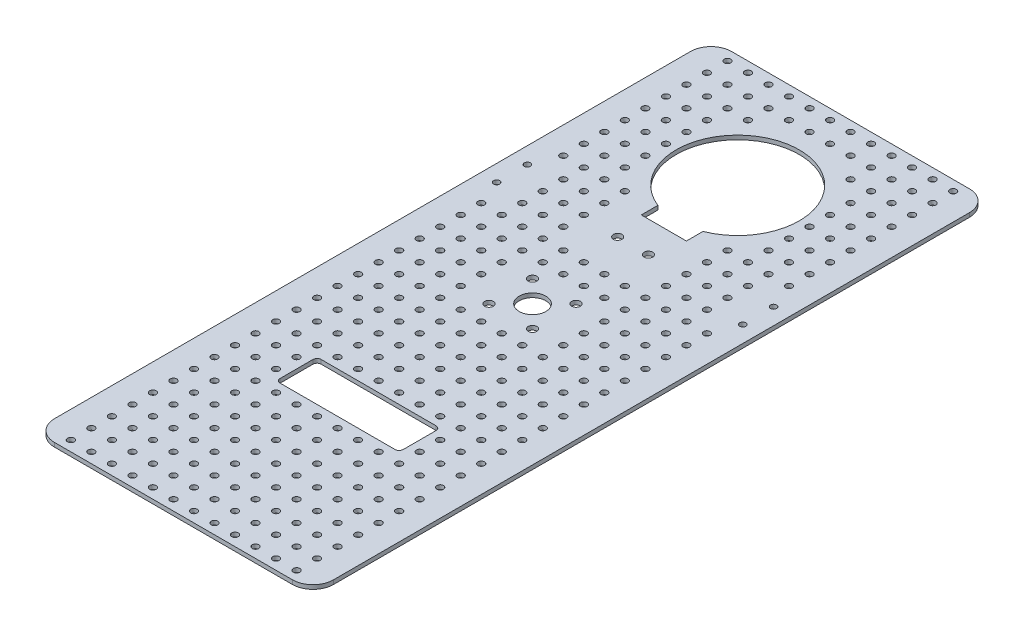
SolidWorks part; units mm, degrees
ref_plane "Спереди" through (0, 0, 0) normal (0, 0, 1) x (1, 0, 0)
ref_plane "Сверху" through (0, 0, 0) normal (0, 1, 0) x (1, 0, 0)
ref_plane "Справа" through (0, 0, 0) normal (1, 0, 0) x (0, 0, -1)
sketch "Эскиз1" plane through (0, 0, 0) normal (0, 1, 0) x (1, 0, 0)
  line L0 (0, 145) -> (0, -185) construction
  line L1 (-68, 145) -> (68, 145)
  line L2 (-68, 145) -> (-68, -185)
  line L3 (-68, -185) -> (68, -185)
  line L4 (68, 145) -> (68, -185)
  line L5 (-68, 0) -> (68, 0) construction
  dimension "D1" = 136
  dimension "D2" = 145
  dimension "D3" = 185
extrude "тело" add sketch "Эскиз1" along normal blind 2
sketch "Эскиз12" plane through (0, 2, 0) normal (0, 1, 0) x (1, 0, 0)
  line L0 (0, 145) -> (0, -185) construction
  line L1 (68, 145) -> (-68, 145) construction
  line L2 (-68, -185) -> (68, -185) construction
  line L3 (60, 47.5) -> (60, 32.5) construction
  line L4 (60, 40) -> (-60, 40) construction
  line L5 (-60, 47.5) -> (-60, 32.5) construction
  circle A0 centre (60, 47.5) radius 1.5
  circle A1 centre (-60, 47.5) radius 1.5
  circle A2 centre (-60, 32.5) radius 1.5
  circle A3 centre (60, 32.5) radius 1.5
  point P12 (-60, 40)
  point P17 (0, 40)
  dimension "D2" = 3
  dimension "D1" = 15
  dimension "D3" = 60
  dimension "D4" = 40
extrude "крепление подвески" cut sketch "Эскиз12" against normal through all
sketch "Эскиз9" plane through (0, 2, 0) normal (0, 1, 0) x (1, 0, 0)
  line L0 (0, -50) -> (0, 50) construction
  line L1 (68, 145) -> (-68, 145) construction
  line L3 (-10.6066, 0.6066) -> (0, -10) construction
  line L4 (0, -10) -> (0, 0) construction
  circle A0 centre (0, -10) radius 6.5
  circle A1 centre (0, -10) radius 15 construction
  circle A2 centre (-10.6066, 0.6066) radius 2.1
  circle A3 centre (10.6066, 0.6066) radius 2.1
  circle A4 centre (10.6066, -20.6066) radius 2.1
  circle A5 centre (-10.6066, -20.6066) radius 2.1
  point P21 (0, -10)
  dimension "D2" = 13
  dimension "D3" = 30
  dimension "D4" = 4.2
  dimension "D1" = 155
  dimension "D5" = 45
  dimension "D6" = 4
extrude "ось вращения качалки" cut sketch "Эскиз9" against normal through all
sketch "Эскиз5" plane through (0, 2, 0) normal (0, 1, 0) x (1, 0, 0)
  line L0 (-50, -171.5) -> (50, -121.5) construction
  line L1 (-50, -121.5) -> (50, -121.5) construction
  line L2 (-50, -121.5) -> (-50, -171.5) construction
  line L3 (-50, -171.5) -> (50, -171.5) construction
  line L4 (50, -121.5) -> (50, -171.5) construction
  line L5 (-50, -121.5) -> (50, -171.5) construction
  line L6 (-68, -185) -> (68, -185) construction
  circle A0 centre (-50, -121.5) radius 1.6
  circle A1 centre (50, -121.5) radius 1.6
  circle A2 centre (50, -171.5) radius 1.6
  circle A3 centre (-50, -171.5) radius 1.6
  point P12 (0, -146.5)
  dimension "D1" = 3.2
  dimension "D2" = 100
  dimension "D3" = 50
  dimension "D4" = 13.5
extrude "Крепление корпуса raspberry" [suppressed] cut sketch "Эскиз5" against normal through all
sketch "Эскиз15" [suppressed] plane through (0, 2, 0) normal (0, 1, 0) x (1, 0, 0)
  line L0 (-22.5, 138.75) -> (22.5, 138.75) construction
  line L1 (68, 145) -> (-68, 145) construction
  circle A0 centre (22.5, 138.75) radius 1.5
  circle A1 centre (-22.5, 138.75) radius 1.5
  point P6 (0, 138.75)
  dimension "D1" = 3
  dimension "D2" = 6.25
  dimension "D3" = 45
extrude "Крепление фронтальной камеры" [suppressed] cut sketch "Эскиз15" against normal up to next
sketch "Эскиз17" plane through (0, 2, 0) normal (0, 1, 0) x (1, 0, 0)
  line L1 (47.5, -137) -> (52.5, -137)
  line L2 (47.5, -137) -> (47.5, -147)
  line L3 (47.5, -147) -> (52.5, -147)
  line L4 (52.5, -137) -> (52.5, -147)
  line L5 (-68, -185) -> (68, -185) construction
  dimension "D1" = 38
  dimension "D2" = 10
  dimension "D3" = 5
extrude "Отверстие под провода питания raspberry" [suppressed] cut sketch "Эскиз17" against normal up to next
sketch "Эскиз18" plane through (0, 2, 0) normal (0, 1, 0) x (1, 0, 0)
  line L0 (0, 0) -> (0, 145) construction
  line L1 (68, 145) -> (-68, 145) construction
  line L2 (-11, 54) -> (11, 54)
  line L3 (11, 54) -> (11, 62.0894)
  line L5 (-11, 62.0894) -> (-11, 54)
  line L6 (68, 145) -> (-68, 145) construction
  line L12 (7.5, 39) -> (-7.5, 39) construction
  circle A1 centre (7.5, 39) radius 2.1
  circle A2 centre (-7.5, 39) radius 2.1
  arc A3 (11, 62.0894) -> (-11, 62.0894) centre (0, 90) ccw
  point P15 (0, 54)
  point P25 (0, 39)
  dimension "D8" = 4.2
  dimension "D3" = 60
  dimension "D1" = 22
  dimension "D2" = 36
  dimension "D4" = 55
  dimension "D9" = 15
  dimension "D10" = 15
fillet "Скругление4" radius 10 2 edges at (68, 1, -145) (-68, 1, -145)
fillet "Скругление6" [suppressed] radius 2
extrude "Вырез под манипулятор" cut sketch "Эскиз18" against normal up to next
fillet "Скругление9" radius 10 2 edges at (68, 1, 185) (-68, 1, 185)
sketch "Эскиз20" plane through (0, 2, 0) normal (0, 1, 0) x (1, 0, 0)
  line L0 (-17.5, -181) -> (17.5, -181) construction
  line L1 (-58, -185) -> (58, -185) construction
  circle A0 centre (-17.5, -181) radius 1.5
  circle A1 centre (17.5, -181) radius 1.5
  point P4 (0, -181)
  point P7 (0, -185)
  dimension "D1" = 3
  dimension "D2" = 4
  dimension "D3" = 35
extrude "Крепление платы раздачи питания с креплением ХТ60" [suppressed] cut sketch "Эскиз20" against normal up to next
sketch "Эскиз21" [suppressed] plane through (0, 2, 0) normal (0, 1, 0) x (1, 0, 0)
  line L0 (-58, -185) -> (58, -185) construction
  line L1 (-35, -43.5) -> (35, -43.5) construction
  line L2 (-35, -43.5) -> (-35, -73.5) construction
  line L3 (-35, -73.5) -> (35, -73.5) construction
  line L4 (35, -43.5) -> (35, -73.5) construction
  circle A0 centre (-35, -43.5) radius 1.6
  circle A1 centre (-35, -73.5) radius 1.6
  circle A2 centre (35, -73.5) radius 1.6
  circle A3 centre (35, -43.5) radius 1.6
  circle A4 centre (50, -121.5) radius 1.6 construction
  point P4 (0, -73.5)
  point P7 (0, -185)
  dimension "D3" = 3.2
  dimension "D1" = 30
  dimension "D2" = 70
  dimension "D4" = 48
extrude "Крепление подставки ServoBoard" [suppressed] cut sketch "Эскиз21" against normal up to next
sketch "Эскиз22" plane through (0, 2, 0) normal (0, 1, 0) x (1, 0, 0)
  line L0 (0, -185) -> (0, 145) construction
  line L1 (-58, -185) -> (58, -185) construction
  line L2 (58, 145) -> (-58, 145) construction
  circle A0 centre (-5, -180) radius 1.6
  circle A1 centre (-15, -180) radius 1.6
  circle A2 centre (-25, -180) radius 1.6
  circle A3 centre (-35, -180) radius 1.6
  circle A4 centre (-45, -180) radius 1.6
  circle A5 centre (-55, -180) radius 1.6
  circle A6 centre (-65, -180) radius 1.6 construction
  circle A7 centre (5, -180) radius 1.6
  circle A8 centre (15, -180) radius 1.6
  circle A9 centre (25, -180) radius 1.6
  circle A10 centre (35, -180) radius 1.6
  circle A11 centre (45, -180) radius 1.6
  circle A12 centre (55, -180) radius 1.6
  circle A13 centre (65, -180) radius 1.6 construction
  circle A14 centre (-5, -170) radius 1.6
  circle A15 centre (-15, -170) radius 1.6
  circle A16 centre (-25, -170) radius 1.6
  circle A17 centre (-35, -170) radius 1.6
  circle A18 centre (-45, -170) radius 1.6
  circle A19 centre (-55, -170) radius 1.6
  circle A20 centre (-65, -170) radius 1.6 construction
  circle A21 centre (5, -170) radius 1.6
  circle A22 centre (15, -170) radius 1.6
  circle A23 centre (25, -170) radius 1.6
  circle A24 centre (35, -170) radius 1.6
  circle A25 centre (45, -170) radius 1.6
  circle A26 centre (55, -170) radius 1.6
  circle A27 centre (65, -170) radius 1.6 construction
  circle A28 centre (-5, -160) radius 1.6
  circle A29 centre (-15, -160) radius 1.6
  circle A30 centre (-25, -160) radius 1.6
  circle A31 centre (-35, -160) radius 1.6
  circle A32 centre (-45, -160) radius 1.6
  circle A33 centre (-55, -160) radius 1.6
  circle A34 centre (-65, -160) radius 1.6 construction
  circle A35 centre (5, -160) radius 1.6
  circle A36 centre (15, -160) radius 1.6
  circle A37 centre (25, -160) radius 1.6
  circle A38 centre (35, -160) radius 1.6
  circle A39 centre (45, -160) radius 1.6
  circle A40 centre (55, -160) radius 1.6
  circle A41 centre (65, -160) radius 1.6 construction
  circle A42 centre (-5, -150) radius 1.6
  circle A43 centre (-15, -150) radius 1.6
  circle A44 centre (-25, -150) radius 1.6
  circle A45 centre (-35, -150) radius 1.6
  circle A46 centre (-45, -150) radius 1.6
  circle A47 centre (-55, -150) radius 1.6
  circle A48 centre (-65, -150) radius 1.6 construction
  circle A49 centre (5, -150) radius 1.6
  circle A50 centre (15, -150) radius 1.6
  circle A51 centre (25, -150) radius 1.6
  circle A52 centre (35, -150) radius 1.6
  circle A53 centre (45, -150) radius 1.6
  circle A54 centre (55, -150) radius 1.6
  circle A55 centre (65, -150) radius 1.6 construction
  circle A56 centre (-5, -140) radius 1.6
  circle A57 centre (-15, -140) radius 1.6
  circle A58 centre (-25, -140) radius 1.6
  circle A59 centre (-35, -140) radius 1.6
  circle A60 centre (-45, -140) radius 1.6
  circle A61 centre (-55, -140) radius 1.6
  circle A62 centre (-65, -140) radius 1.6 construction
  circle A63 centre (5, -140) radius 1.6
  circle A64 centre (15, -140) radius 1.6
  circle A65 centre (25, -140) radius 1.6
  circle A66 centre (35, -140) radius 1.6
  circle A67 centre (45, -140) radius 1.6
  circle A68 centre (55, -140) radius 1.6
  circle A69 centre (65, -140) radius 1.6 construction
  circle A70 centre (-5, -130) radius 1.6
  circle A71 centre (-15, -130) radius 1.6
  circle A72 centre (-25, -130) radius 1.6
  circle A73 centre (-35, -130) radius 1.6
  circle A74 centre (-45, -130) radius 1.6
  circle A75 centre (-55, -130) radius 1.6
  circle A76 centre (-65, -130) radius 1.6 construction
  circle A77 centre (5, -130) radius 1.6
  circle A78 centre (15, -130) radius 1.6
  circle A79 centre (25, -130) radius 1.6
  circle A80 centre (35, -130) radius 1.6
  circle A81 centre (45, -130) radius 1.6
  circle A82 centre (55, -130) radius 1.6
  circle A83 centre (65, -130) radius 1.6 construction
  circle A84 centre (-5, -120) radius 1.6
  circle A85 centre (-15, -120) radius 1.6
  circle A86 centre (-25, -120) radius 1.6
  circle A87 centre (-35, -120) radius 1.6
  circle A88 centre (-45, -120) radius 1.6
  circle A89 centre (-55, -120) radius 1.6
  circle A90 centre (-65, -120) radius 1.6 construction
  circle A91 centre (5, -120) radius 1.6
  circle A92 centre (15, -120) radius 1.6
  circle A93 centre (25, -120) radius 1.6
  circle A94 centre (35, -120) radius 1.6
  circle A95 centre (45, -120) radius 1.6
  circle A96 centre (55, -120) radius 1.6
  circle A97 centre (65, -120) radius 1.6 construction
  circle A98 centre (-5, -110) radius 1.6
  circle A99 centre (-15, -110) radius 1.6
  circle A100 centre (-25, -110) radius 1.6
  circle A101 centre (-35, -110) radius 1.6
  circle A102 centre (-45, -110) radius 1.6
  circle A103 centre (-55, -110) radius 1.6
  circle A104 centre (-65, -110) radius 1.6 construction
  circle A105 centre (5, -110) radius 1.6
  circle A106 centre (15, -110) radius 1.6
  circle A107 centre (25, -110) radius 1.6
  circle A108 centre (35, -110) radius 1.6
  circle A109 centre (45, -110) radius 1.6
  circle A110 centre (55, -110) radius 1.6
  circle A111 centre (65, -110) radius 1.6 construction
  circle A112 centre (-5, -100) radius 1.6 construction
  circle A113 centre (-15, -100) radius 1.6 construction
  circle A114 centre (-25, -100) radius 1.6 construction
  circle A115 centre (-35, -100) radius 1.6
  circle A116 centre (-45, -100) radius 1.6
  circle A117 centre (-55, -100) radius 1.6
  circle A118 centre (-65, -100) radius 1.6 construction
  circle A119 centre (5, -100) radius 1.6 construction
  circle A120 centre (15, -100) radius 1.6 construction
  circle A121 centre (25, -100) radius 1.6 construction
  circle A122 centre (35, -100) radius 1.6
  circle A123 centre (45, -100) radius 1.6
  circle A124 centre (55, -100) radius 1.6
  circle A125 centre (65, -100) radius 1.6 construction
  circle A126 centre (-5, -90) radius 1.6 construction
  circle A127 centre (-15, -90) radius 1.6 construction
  circle A128 centre (-25, -90) radius 1.6 construction
  circle A129 centre (-35, -90) radius 1.6
  circle A130 centre (-45, -90) radius 1.6
  circle A131 centre (-55, -90) radius 1.6
  circle A132 centre (-65, -90) radius 1.6 construction
  circle A133 centre (5, -90) radius 1.6 construction
  circle A134 centre (15, -90) radius 1.6 construction
  circle A135 centre (25, -90) radius 1.6 construction
  circle A136 centre (35, -90) radius 1.6
  circle A137 centre (45, -90) radius 1.6
  circle A138 centre (55, -90) radius 1.6
  circle A139 centre (65, -90) radius 1.6 construction
  circle A140 centre (-5, -80) radius 1.6
  circle A141 centre (-15, -80) radius 1.6
  circle A142 centre (-25, -80) radius 1.6
  circle A143 centre (-35, -80) radius 1.6
  circle A144 centre (-45, -80) radius 1.6
  circle A145 centre (-55, -80) radius 1.6
  circle A146 centre (-65, -80) radius 1.6 construction
  circle A147 centre (5, -80) radius 1.6
  circle A148 centre (15, -80) radius 1.6
  circle A149 centre (25, -80) radius 1.6
  circle A150 centre (35, -80) radius 1.6
  circle A151 centre (45, -80) radius 1.6
  circle A152 centre (55, -80) radius 1.6
  circle A153 centre (65, -80) radius 1.6 construction
  circle A154 centre (-5, -70) radius 1.6
  circle A155 centre (-15, -70) radius 1.6
  circle A156 centre (-25, -70) radius 1.6
  circle A157 centre (-35, -70) radius 1.6
  circle A158 centre (-45, -70) radius 1.6
  circle A159 centre (-55, -70) radius 1.6
  circle A160 centre (-65, -70) radius 1.6 construction
  circle A161 centre (5, -70) radius 1.6
  circle A162 centre (15, -70) radius 1.6
  circle A163 centre (25, -70) radius 1.6
  circle A164 centre (35, -70) radius 1.6
  circle A165 centre (45, -70) radius 1.6
  circle A166 centre (55, -70) radius 1.6
  circle A167 centre (65, -70) radius 1.6 construction
  circle A168 centre (-5, -60) radius 1.6
  circle A169 centre (-15, -60) radius 1.6
  circle A170 centre (-25, -60) radius 1.6
  circle A171 centre (-35, -60) radius 1.6
  circle A172 centre (-45, -60) radius 1.6
  circle A173 centre (-55, -60) radius 1.6
  circle A174 centre (-65, -60) radius 1.6 construction
  circle A175 centre (5, -60) radius 1.6
  circle A176 centre (15, -60) radius 1.6
  circle A177 centre (25, -60) radius 1.6
  circle A178 centre (35, -60) radius 1.6
  circle A179 centre (45, -60) radius 1.6
  circle A180 centre (55, -60) radius 1.6
  circle A181 centre (65, -60) radius 1.6 construction
  circle A182 centre (-5, -50) radius 1.6
  circle A183 centre (-15, -50) radius 1.6
  circle A184 centre (-25, -50) radius 1.6
  circle A185 centre (-35, -50) radius 1.6
  circle A186 centre (-45, -50) radius 1.6
  circle A187 centre (-55, -50) radius 1.6
  circle A188 centre (-65, -50) radius 1.6 construction
  circle A189 centre (5, -50) radius 1.6
  circle A190 centre (15, -50) radius 1.6
  circle A191 centre (25, -50) radius 1.6
  circle A192 centre (35, -50) radius 1.6
  circle A193 centre (45, -50) radius 1.6
  circle A194 centre (55, -50) radius 1.6
  circle A195 centre (65, -50) radius 1.6 construction
  circle A196 centre (-5, -40) radius 1.6
  circle A197 centre (-15, -40) radius 1.6
  circle A198 centre (-25, -40) radius 1.6
  circle A199 centre (-35, -40) radius 1.6
  circle A200 centre (-45, -40) radius 1.6
  circle A201 centre (-55, -40) radius 1.6
  circle A202 centre (-65, -40) radius 1.6 construction
  circle A203 centre (5, -40) radius 1.6
  circle A204 centre (15, -40) radius 1.6
  circle A205 centre (25, -40) radius 1.6
  circle A206 centre (35, -40) radius 1.6
  circle A207 centre (45, -40) radius 1.6
  circle A208 centre (55, -40) radius 1.6
  circle A209 centre (65, -40) radius 1.6 construction
  circle A210 centre (-5, -30) radius 1.6
  circle A211 centre (-15, -30) radius 1.6
  circle A212 centre (-25, -30) radius 1.6
  circle A213 centre (-35, -30) radius 1.6
  circle A214 centre (-45, -30) radius 1.6
  circle A215 centre (-55, -30) radius 1.6
  circle A216 centre (-65, -30) radius 1.6 construction
  circle A217 centre (5, -30) radius 1.6
  circle A218 centre (15, -30) radius 1.6
  circle A219 centre (25, -30) radius 1.6
  circle A220 centre (35, -30) radius 1.6
  circle A221 centre (45, -30) radius 1.6
  circle A222 centre (55, -30) radius 1.6
  circle A223 centre (65, -30) radius 1.6 construction
  circle A226 centre (-25, -20) radius 1.6
  circle A227 centre (-35, -20) radius 1.6
  circle A228 centre (-45, -20) radius 1.6
  circle A229 centre (-55, -20) radius 1.6
  circle A230 centre (-65, -20) radius 1.6 construction
  circle A233 centre (25, -20) radius 1.6
  circle A234 centre (35, -20) radius 1.6
  circle A235 centre (45, -20) radius 1.6
  circle A236 centre (55, -20) radius 1.6
  circle A237 centre (65, -20) radius 1.6 construction
  circle A240 centre (-25, -10) radius 1.6
  circle A241 centre (-35, -10) radius 1.6
  circle A242 centre (-45, -10) radius 1.6
  circle A243 centre (-55, -10) radius 1.6
  circle A244 centre (-65, -10) radius 1.6 construction
  circle A247 centre (25, -10) radius 1.6
  circle A248 centre (35, -10) radius 1.6
  circle A249 centre (45, -10) radius 1.6
  circle A250 centre (55, -10) radius 1.6
  circle A251 centre (65, -10) radius 1.6 construction
  circle A254 centre (-25, 0) radius 1.6
  circle A255 centre (-35, 0) radius 1.6
  circle A256 centre (-45, 0) radius 1.6
  circle A257 centre (-55, 0) radius 1.6
  circle A258 centre (-65, 0) radius 1.6 construction
  circle A261 centre (25, 0) radius 1.6
  circle A262 centre (35, 0) radius 1.6
  circle A263 centre (45, 0) radius 1.6
  circle A264 centre (55, 0) radius 1.6
  circle A265 centre (65, 0) radius 1.6 construction
  circle A266 centre (-5, 10) radius 1.6
  circle A267 centre (-15, 10) radius 1.6
  circle A268 centre (-25, 10) radius 1.6
  circle A269 centre (-35, 10) radius 1.6
  circle A270 centre (-45, 10) radius 1.6
  circle A271 centre (-55, 10) radius 1.6
  circle A272 centre (-65, 10) radius 1.6 construction
  circle A273 centre (5, 10) radius 1.6
  circle A274 centre (15, 10) radius 1.6
  circle A275 centre (25, 10) radius 1.6
  circle A276 centre (35, 10) radius 1.6
  circle A277 centre (45, 10) radius 1.6
  circle A278 centre (55, 10) radius 1.6
  circle A279 centre (65, 10) radius 1.6 construction
  circle A280 centre (-5, 20) radius 1.6
  circle A281 centre (-15, 20) radius 1.6
  circle A282 centre (-25, 20) radius 1.6
  circle A283 centre (-35, 20) radius 1.6
  circle A284 centre (-45, 20) radius 1.6
  circle A285 centre (-55, 20) radius 1.6
  circle A286 centre (-65, 20) radius 1.6 construction
  circle A287 centre (5, 20) radius 1.6
  circle A288 centre (15, 20) radius 1.6
  circle A289 centre (25, 20) radius 1.6
  circle A290 centre (35, 20) radius 1.6
  circle A291 centre (45, 20) radius 1.6
  circle A292 centre (55, 20) radius 1.6
  circle A293 centre (65, 20) radius 1.6 construction
  circle A294 centre (-5, 30) radius 1.6 construction
  circle A295 centre (-15, 30) radius 1.6 construction
  circle A296 centre (-25, 30) radius 1.6
  circle A297 centre (-35, 30) radius 1.6
  circle A298 centre (-45, 30) radius 1.6
  circle A299 centre (-55, 30) radius 1.6 construction
  circle A300 centre (-65, 30) radius 1.6 construction
  circle A301 centre (5, 30) radius 1.6 construction
  circle A302 centre (15, 30) radius 1.6 construction
  circle A303 centre (25, 30) radius 1.6
  circle A304 centre (35, 30) radius 1.6
  circle A305 centre (45, 30) radius 1.6
  circle A306 centre (55, 30) radius 1.6 construction
  circle A307 centre (65, 30) radius 1.6 construction
  circle A309 centre (-15, 40) radius 1.6 construction
  circle A310 centre (-25, 40) radius 1.6
  circle A311 centre (-35, 40) radius 1.6
  circle A312 centre (-45, 40) radius 1.6
  circle A313 centre (-55, 40) radius 1.6 construction
  circle A314 centre (-65, 40) radius 1.6 construction
  circle A316 centre (15, 40) radius 1.6 construction
  circle A317 centre (25, 40) radius 1.6
  circle A318 centre (35, 40) radius 1.6
  circle A319 centre (45, 40) radius 1.6
  circle A320 centre (55, 40) radius 1.6 construction
  circle A321 centre (65, 40) radius 1.6 construction
  circle A323 centre (-15, 50) radius 1.6 construction
  circle A324 centre (-25, 50) radius 1.6
  circle A325 centre (-35, 50) radius 1.6
  circle A326 centre (-45, 50) radius 1.6
  circle A327 centre (-55, 50) radius 1.6 construction
  circle A328 centre (-65, 50) radius 1.6 construction
  circle A330 centre (15, 50) radius 1.6 construction
  circle A331 centre (25, 50) radius 1.6
  circle A332 centre (35, 50) radius 1.6
  circle A333 centre (45, 50) radius 1.6
  circle A334 centre (55, 50) radius 1.6 construction
  circle A335 centre (65, 50) radius 1.6 construction
  circle A337 centre (-15, 60) radius 1.6 construction
  circle A338 centre (-25, 60) radius 1.6
  circle A339 centre (-35, 60) radius 1.6
  circle A340 centre (-45, 60) radius 1.6
  circle A341 centre (-55, 60) radius 1.6
  circle A342 centre (-65, 60) radius 1.6 construction
  circle A344 centre (15, 60) radius 1.6 construction
  circle A345 centre (25, 60) radius 1.6
  circle A346 centre (35, 60) radius 1.6
  circle A347 centre (45, 60) radius 1.6
  circle A348 centre (55, 60) radius 1.6
  circle A349 centre (65, 60) radius 1.6 construction
  circle A352 centre (-25, 70) radius 1.6 construction
  circle A353 centre (-35, 70) radius 1.6
  circle A354 centre (-45, 70) radius 1.6
  circle A355 centre (-55, 70) radius 1.6
  circle A356 centre (-65, 70) radius 1.6 construction
  circle A359 centre (25, 70) radius 1.6 construction
  circle A360 centre (35, 70) radius 1.6
  circle A361 centre (45, 70) radius 1.6
  circle A362 centre (55, 70) radius 1.6
  circle A363 centre (65, 70) radius 1.6 construction
  circle A367 centre (-35, 80) radius 1.6
  circle A368 centre (-45, 80) radius 1.6
  circle A369 centre (-55, 80) radius 1.6
  circle A370 centre (-65, 80) radius 1.6 construction
  circle A374 centre (35, 80) radius 1.6
  circle A375 centre (45, 80) radius 1.6
  circle A376 centre (55, 80) radius 1.6
  circle A377 centre (65, 80) radius 1.6 construction
  circle A381 centre (-35, 90) radius 1.6
  circle A382 centre (-45, 90) radius 1.6
  circle A383 centre (-55, 90) radius 1.6
  circle A384 centre (-65, 90) radius 1.6 construction
  circle A388 centre (35, 90) radius 1.6
  circle A389 centre (45, 90) radius 1.6
  circle A390 centre (55, 90) radius 1.6
  circle A391 centre (65, 90) radius 1.6 construction
  circle A395 centre (-35, 100) radius 1.6
  circle A396 centre (-45, 100) radius 1.6
  circle A397 centre (-55, 100) radius 1.6
  circle A398 centre (-65, 100) radius 1.6 construction
  circle A402 centre (35, 100) radius 1.6
  circle A403 centre (45, 100) radius 1.6
  circle A404 centre (55, 100) radius 1.6
  circle A405 centre (65, 100) radius 1.6 construction
  circle A408 centre (-25, 110) radius 1.6 construction
  circle A409 centre (-35, 110) radius 1.6
  circle A410 centre (-45, 110) radius 1.6
  circle A411 centre (-55, 110) radius 1.6
  circle A412 centre (-65, 110) radius 1.6 construction
  circle A415 centre (25, 110) radius 1.6 construction
  circle A416 centre (35, 110) radius 1.6
  circle A417 centre (45, 110) radius 1.6
  circle A418 centre (55, 110) radius 1.6
  circle A419 centre (65, 110) radius 1.6 construction
  circle A421 centre (-15, 120) radius 1.6 construction
  circle A422 centre (-25, 120) radius 1.6
  circle A423 centre (-35, 120) radius 1.6
  circle A424 centre (-45, 120) radius 1.6
  circle A425 centre (-55, 120) radius 1.6
  circle A426 centre (-65, 120) radius 1.6 construction
  circle A428 centre (15, 120) radius 1.6 construction
  circle A429 centre (25, 120) radius 1.6
  circle A430 centre (35, 120) radius 1.6
  circle A431 centre (45, 120) radius 1.6
  circle A432 centre (55, 120) radius 1.6
  circle A433 centre (65, 120) radius 1.6 construction
  circle A434 centre (-5, 130) radius 1.6
  circle A435 centre (-15, 130) radius 1.6
  circle A436 centre (-25, 130) radius 1.6
  circle A437 centre (-35, 130) radius 1.6
  circle A438 centre (-45, 130) radius 1.6
  circle A439 centre (-55, 130) radius 1.6
  circle A440 centre (-65, 130) radius 1.6 construction
  circle A441 centre (5, 130) radius 1.6
  circle A442 centre (15, 130) radius 1.6
  circle A443 centre (25, 130) radius 1.6
  circle A444 centre (35, 130) radius 1.6
  circle A445 centre (45, 130) radius 1.6
  circle A446 centre (55, 130) radius 1.6
  circle A447 centre (65, 130) radius 1.6 construction
  circle A448 centre (-5, 140) radius 1.6
  circle A449 centre (-15, 140) radius 1.6
  circle A450 centre (-25, 140) radius 1.6
  circle A451 centre (-35, 140) radius 1.6
  circle A452 centre (-45, 140) radius 1.6
  circle A453 centre (-55, 140) radius 1.6
  circle A454 centre (-65, 140) radius 1.6 construction
  circle A455 centre (5, 140) radius 1.6
  circle A456 centre (15, 140) radius 1.6
  circle A457 centre (25, 140) radius 1.6
  circle A458 centre (35, 140) radius 1.6
  circle A459 centre (45, 140) radius 1.6
  circle A460 centre (55, 140) radius 1.6
  circle A461 centre (65, 140) radius 1.6 construction
  circle A462 centre (-5, -20) radius 1.6 construction
  circle A463 centre (-15, -20) radius 1.6 construction
  circle A464 centre (5, -20) radius 1.6 construction
  circle A465 centre (15, -20) radius 1.6 construction
  circle A466 centre (-5, -10) radius 1.6 construction
  circle A467 centre (-15, -10) radius 1.6 construction
  circle A468 centre (5, -10) radius 1.6 construction
  circle A469 centre (15, -10) radius 1.6 construction
  circle A470 centre (-5, 0) radius 1.6 construction
  circle A471 centre (-15, 0) radius 1.6 construction
  circle A472 centre (5, 0) radius 1.6 construction
  circle A473 centre (15, 0) radius 1.6 construction
  circle A474 centre (-5, 40) radius 1.6 [skipped]
  circle A475 centre (5, 40) radius 1.6 [skipped]
  circle A476 centre (-5, 50) radius 1.6 [skipped]
  circle A477 centre (5, 50) radius 1.6 [skipped]
  circle A478 centre (-5, 70) radius 1.6 [skipped]
  circle A479 centre (-15, 70) radius 1.6 [skipped]
  circle A480 centre (5, 70) radius 1.6 [skipped]
  circle A481 centre (15, 70) radius 1.6 [skipped]
  circle A482 centre (-5, 80) radius 1.6 [skipped]
  circle A483 centre (-15, 80) radius 1.6 [skipped]
  circle A484 centre (5, 80) radius 1.6 [skipped]
  circle A485 centre (15, 80) radius 1.6 [skipped]
  circle A486 centre (-5, 90) radius 1.6 [skipped]
  circle A487 centre (-15, 90) radius 1.6 [skipped]
  circle A488 centre (5, 90) radius 1.6 [skipped]
  circle A489 centre (15, 90) radius 1.6 [skipped]
  circle A490 centre (-5, 100) radius 1.6 [skipped]
  circle A491 centre (-15, 100) radius 1.6 [skipped]
  circle A492 centre (5, 100) radius 1.6 [skipped]
  circle A493 centre (15, 100) radius 1.6 [skipped]
  circle A494 centre (-5, 110) radius 1.6 [skipped]
  circle A495 centre (-15, 110) radius 1.6 [skipped]
  circle A496 centre (5, 110) radius 1.6 [skipped]
  circle A497 centre (15, 110) radius 1.6 [skipped]
  circle A498 centre (25, 80) radius 1.6 [skipped]
  circle A499 centre (25, 90) radius 1.6 [skipped]
  circle A500 centre (25, 100) radius 1.6 [skipped]
  circle A501 centre (-25, 80) radius 1.6 [skipped]
  circle A502 centre (-25, 90) radius 1.6 [skipped]
  circle A503 centre (-25, 100) radius 1.6 [skipped]
  circle A504 centre (-5, 60) radius 1.6 [skipped]
  circle A505 centre (5, 60) radius 1.6 [skipped]
  circle A506 centre (-5, 120) radius 1.6 [skipped]
  circle A507 centre (5, 120) radius 1.6 [skipped]
  dimension "D1" = 3.2
  dimension "D7" = 10
  dimension "D8" = 10
  dimension "D9" = 10
  dimension "D2" = 5
  dimension "D3" = 5
  dimension "D4" = 7
  dimension "D5" = 8
  dimension "D6" = 33
extrude "Сетка 10мм" cut sketch "Эскиз22" against normal up to next (2 mm away)
sketch "Эскиз11" plane through (0, 2, 0) normal (0, 1, 0) x (1, 0, 0)
  line L0 (-30, -95) -> (30, -95) construction
  line L1 (-30, -85) -> (30, -85)
  line L2 (-30, -85) -> (-30, -105)
  line L3 (-30, -105) -> (30, -105)
  line L4 (30, -85) -> (30, -105)
  line L5 (-58, -185) -> (58, -185) construction
  point P11 (0, -85)
  dimension "D3" = 80
  dimension "D1" = 60
  dimension "D2" = 20
extrude "отверстие под провода на нижний этаж" cut sketch "Эскиз11" against normal through all
fillet "Скругление3" radius 2 4 edges at (-30, 1, 105) (30, 1, 105) (30, 1, 85) (-30, 1, 85)
